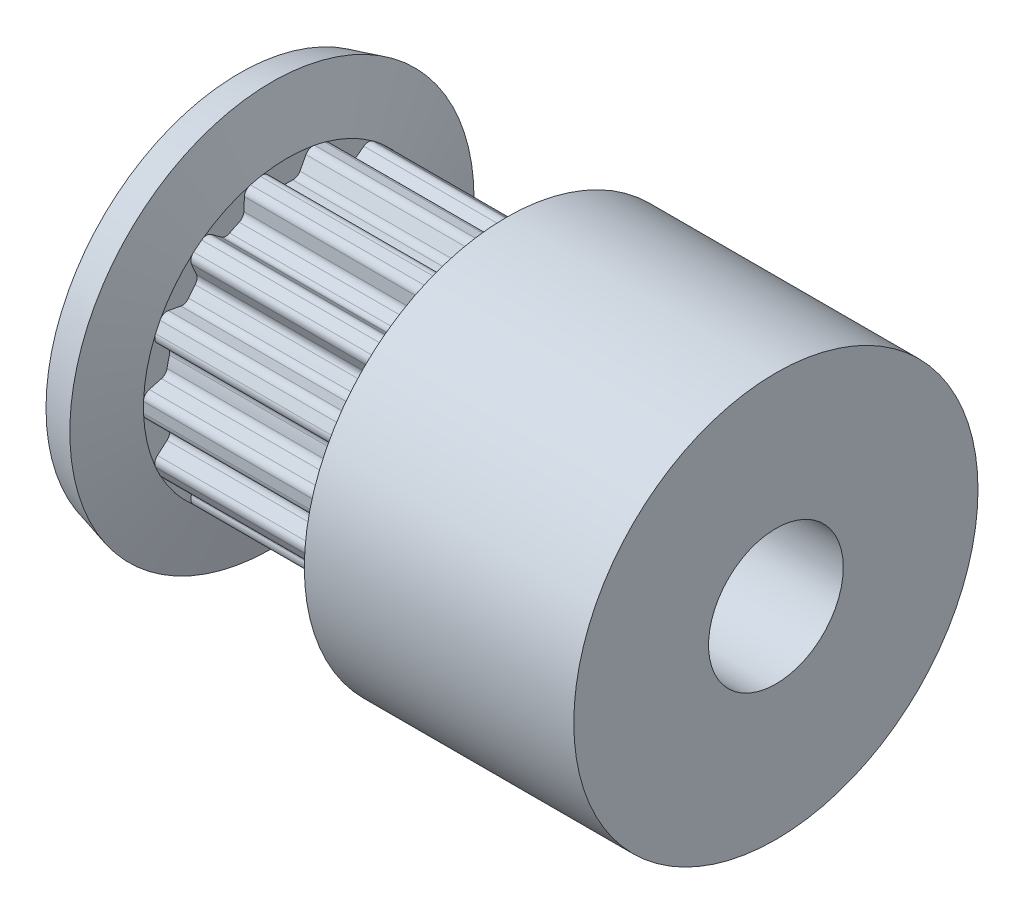
SolidWorks part; units mm, degrees
ref_plane "Front Plane" through (0, 0, 0) normal (0, 0, 1) x (1, 0, 0)
ref_plane "Top Plane" through (0, 0, 0) normal (0, 1, 0) x (1, 0, 0)
ref_plane "Right Plane" through (0, 0, 0) normal (1, 0, 0) x (0, 0, -1)
sketch "Sketch1" plane through (0, 0, 0) normal (0, 0, 1) x (1, 0, 0)
  line L0 (1, 4.1433) -> (1, 0)
  line L1 (1, 0) -> (16.5, 0)
  line L2 (16.5, 0) -> (16.5, 6)
  line L3 (16.5, 6) -> (8, 6)
  line L4 (8, 6) -> (8, 3.635)
  line L5 (8, 3.635) -> (2, 3.635)
  line L6 (2, 3.635) -> (2, 4.275)
  line L7 (2, 4.275) -> (1.5378, 6)
  line L8 (1.5378, 6) -> (0.5719, 5.7412)
  line L9 (0.5719, 5.7412) -> (1, 4.1433)
  line L10 (0.5719, 0) -> (16.5, 0) construction
revolve "Revolve1" add sketch "Sketch1" angle 360 about L10 reverse direction yes
ref_plane "Plane1" through (0, 0, 0) normal (0, 0, -1) x (-1, 0, 0)
sketch "Sketch2" plane through (0, 0, 0) normal (0, 0, -1) x (-1, 0, 0)
  line L0 (-1, 3) -> (-1, 0)
  line L1 (-1, 0) -> (0, 0)
  line L2 (0, 0) -> (0, 3)
  line L3 (0, 3) -> (-1, 3)
  line L4 (-1, 0) -> (0, 0) construction
revolve "Revolve2" add sketch "Sketch2" angle 360 about L4 reverse direction yes
hole_wizard "Ø4.0 (4) Diameter Hole1" positions "Sketch4" profile "Sketch3" hole size "Ø4.0" standard "ANSI Metric"
sketch "Sketch4" plane through (16.5, 0, 0) normal (1, 0, 0) x (0, 0, -1)
  point P0 (0, 0)
sketch "Sketch3" plane through (16.5, 0, 0) normal (0, 1, 0) x (0, 0, -1)
  line L0 (0, 0) -> (0, 16.5)
  line L1 (0, 16.5) -> (2, 16.5)
  line L2 (2, 16.5) -> (2, 0)
  line L5 (2, 0) -> (0, 0)
  line L11 (0, -6.35) -> (0, 107.95) construction
  dimension "Thru Hole Dia." = 4
  dimension "Thru Hole Depth" = 16.5
sketch "Sketch5" plane through (0, 0, 0) normal (0, 1, 0) x (1, 0, 0)
  line L0 (8, 4.275) -> (2, 4.275)
rib "Rib1" sketch "Sketch5" sketch "Sketch5" thickness 0.6584 extrusion direction parallel to sketch draft on yes draft angle 15.143 parameters "D1"=0.6584, "D3"=15.143
ref_plane "Plane2" through (0, 0, 0) normal (0, -1, 0) x (1, 0, 0)
sketch "Sketch6" plane through (0, 0, 0) normal (0, -1, 0) x (1, 0, 0)
  line L0 (8, 4.275) -> (2, 4.275)
rib "Rib2" sketch "Sketch6" sketch "Sketch6" thickness 0.6584 extrusion direction parallel to sketch draft on yes draft angle 15.143 parameters "D1"=0.6584, "D3"=15.143
ref_plane "Plane3" through (0, 0, 0) normal (0, 0.6235, -0.7818) x (-1, 0, 0)
sketch "Sketch7" plane through (0, 0, 0) normal (0, 0.6235, -0.7818) x (-1, 0, 0)
  line L0 (-8, -4.275) -> (-2, -4.275)
rib "Rib3" sketch "Sketch7" sketch "Sketch7" thickness 0.6584 extrusion direction parallel to sketch draft on yes draft angle 15.143 parameters "D1"=0.6584, "D3"=15.143
ref_plane "Plane4" through (0, 0, 0) normal (0, -0.6235, -0.7818) x (1, 0, 0)
sketch "Sketch8" plane through (0, 0, 0) normal (0, -0.6235, -0.7818) x (1, 0, 0)
  line L0 (8, 4.275) -> (2, 4.275)
rib "Rib4" sketch "Sketch8" sketch "Sketch8" thickness 0.6584 extrusion direction parallel to sketch draft on yes draft angle 15.143 parameters "D1"=0.6584, "D3"=15.143
ref_plane "Plane5" through (0, 0, 0) normal (0, -0.901, -0.4339) x (1, 0, 0)
sketch "Sketch9" plane through (0, 0, 0) normal (0, -0.901, -0.4339) x (1, 0, 0)
  line L0 (8, 4.275) -> (2, 4.275)
rib "Rib5" sketch "Sketch9" sketch "Sketch9" thickness 0.6584 extrusion direction parallel to sketch draft on yes draft angle 15.143 parameters "D1"=0.6584, "D3"=15.143
ref_plane "Plane6" through (0, 0, 0) normal (0, 0.901, 0.4339) x (-1, 0, 0)
sketch "Sketch10" plane through (0, 0, 0) normal (0, 0.901, 0.4339) x (-1, 0, 0)
  line L0 (-8, -4.275) -> (-2, -4.275)
rib "Rib6" sketch "Sketch10" sketch "Sketch10" thickness 0.6584 extrusion direction parallel to sketch draft on yes draft angle 15.143 parameters "D1"=0.6584, "D3"=15.143
ref_plane "Plane7" through (0, 0, 0) normal (0, 0.901, -0.4339) x (-1, 0, 0)
sketch "Sketch11" plane through (0, 0, 0) normal (0, 0.901, -0.4339) x (-1, 0, 0)
  line L0 (-8, -4.275) -> (-2, -4.275)
rib "Rib7" sketch "Sketch11" sketch "Sketch11" thickness 0.6584 extrusion direction parallel to sketch draft on yes draft angle 15.143 parameters "D1"=0.6584, "D3"=15.143
ref_plane "Plane8" through (0, 0, 0) normal (0, 0.2225, -0.9749) x (-1, 0, 0)
sketch "Sketch12" plane through (0, 0, 0) normal (0, 0.2225, -0.9749) x (-1, 0, 0)
  line L0 (-8, -4.275) -> (-2, -4.275)
rib "Rib8" sketch "Sketch12" sketch "Sketch12" thickness 0.6584 extrusion direction parallel to sketch draft on yes draft angle 15.143 parameters "D1"=0.6584, "D3"=15.143
ref_plane "Plane9" through (0, 0, 0) normal (0, -0.2225, -0.9749) x (1, 0, 0)
sketch "Sketch13" plane through (0, 0, 0) normal (0, -0.2225, -0.9749) x (1, 0, 0)
  line L0 (8, 4.275) -> (2, 4.275)
rib "Rib9" sketch "Sketch13" sketch "Sketch13" thickness 0.6584 extrusion direction parallel to sketch draft on yes draft angle 15.143 parameters "D1"=0.6584, "D3"=15.143
sketch "Sketch14" plane through (0, 0, 0) normal (0, -0.2225, -0.9749) x (1, 0, 0)
  line L0 (2, -4.275) -> (8, -4.275)
rib "Rib10" sketch "Sketch14" sketch "Sketch14" thickness 0.6584 extrusion direction parallel to sketch draft on yes draft angle 15.143 parameters "D1"=0.6584, "D3"=15.143
ref_plane "Plane10" through (0, 0, 0) normal (0, -0.2225, 0.9749) x (1, 0, 0)
sketch "Sketch15" plane through (0, 0, 0) normal (0, -0.2225, 0.9749) x (1, 0, 0)
  line L0 (8, 4.275) -> (2, 4.275)
rib "Rib11" sketch "Sketch15" sketch "Sketch15" thickness 0.6584 extrusion direction parallel to sketch draft on yes draft angle 15.143 parameters "D1"=0.6584, "D3"=15.143
ref_plane "Plane11" through (0, 0, 0) normal (0, -0.901, 0.4339) x (1, 0, 0)
sketch "Sketch16" plane through (0, 0, 0) normal (0, -0.901, 0.4339) x (1, 0, 0)
  line L0 (8, 4.275) -> (2, 4.275)
rib "Rib12" sketch "Sketch16" sketch "Sketch16" thickness 0.6584 extrusion direction parallel to sketch draft on yes draft angle 15.143 parameters "D1"=0.6584, "D3"=15.143
ref_plane "Plane12" through (0, 0, 0) normal (0, -0.6235, 0.7818) x (1, 0, 0)
sketch "Sketch17" plane through (0, 0, 0) normal (0, -0.6235, 0.7818) x (1, 0, 0)
  line L0 (8, 4.275) -> (2, 4.275)
rib "Rib13" sketch "Sketch17" sketch "Sketch17" thickness 0.6584 extrusion direction parallel to sketch draft on yes draft angle 15.143 parameters "D1"=0.6584, "D3"=15.143
sketch "Sketch18" plane through (0, 0, 0) normal (0, -0.6235, -0.7818) x (1, 0, 0)
  line L0 (2, -4.275) -> (8, -4.275)
rib "Rib14" sketch "Sketch18" sketch "Sketch18" thickness 0.6584 extrusion direction parallel to sketch draft on yes draft angle 15.143 parameters "D1"=0.6584, "D3"=15.143
chamfer "Chamfer1" distance 1.5 angle 18.435 1 edges at (8, 0, -6) first distance on face at (8, 0, -6)
fillet "Fillet1" radius 0.23 56 edges at (5, -3.133, 1.8433) (5, 3.3945, 1.3002) (5, 3.133, -1.8433) (4.9983, -0.3292, 4.275) (5, 1.0999, 3.4646) (4.9983, 0.3292, 4.275) (5, -1.0999, -3.4646) (5, 0.5122, 3.5987) (5, 3.6225, -0.3014) (4.9983, 3.1371, -2.9228) (5, 2.4942, 2.6442) (5, 2.4942, -2.6442) (5, -0.5122, 3.5987) (4.9983, 2.1515, -3.7088) (5, -3.3945, -1.3002) (4.9983, 1.5582, -3.9945) (5, 2.0229, -3.0201) (5, 1.0999, -3.4646) (4.9983, 4.0946, -1.2722) (4.9983, 0.3292, -4.275) (4.9983, 4.2411, 0.6303) (4.9983, -0.3292, -4.275) (4.9983, 3.5476, 2.408) (5, -0.5122, -3.5987) (4.9983, 2.1515, 3.7088) (4.9983, -1.5582, -3.9945) (5, -1.0999, 3.4646) (4.9983, -2.1515, -3.7088) (5, -2.0229, 3.0201) (5, -2.0229, -3.0201) (5, -3.6225, 0.3014) (4.9983, -3.1371, -2.9228) (5, -2.4942, -2.6442) (4.9983, -3.5476, -2.408) (5, 0.5122, -3.5987) (5, -3.133, -1.8433) (4.9983, 3.5476, -2.408) (4.9983, -4.0946, -1.2722) (5, 3.3945, -1.3002) (4.9983, -4.2411, -0.6303) (4.9983, 4.2411, -0.6303) (5, -3.6225, -0.3014) (5, 3.6225, 0.3014) (4.9983, -4.2411, 0.6303) (4.9983, 4.0946, 1.2722) (4.9983, -4.0946, 1.2722) (5, 3.133, 1.8433) (5, -3.3945, 1.3002) (4.9983, 3.1371, 2.9228) (4.9983, -3.5476, 2.408) (5, 2.0229, 3.0201) (4.9983, -3.1371, 2.9228) (4.9983, 1.5582, 3.9945) (5, -2.4942, 2.6442) (4.9983, -2.1515, 3.7088) (4.9983, -1.5582, 3.9945) tangent propagation no
